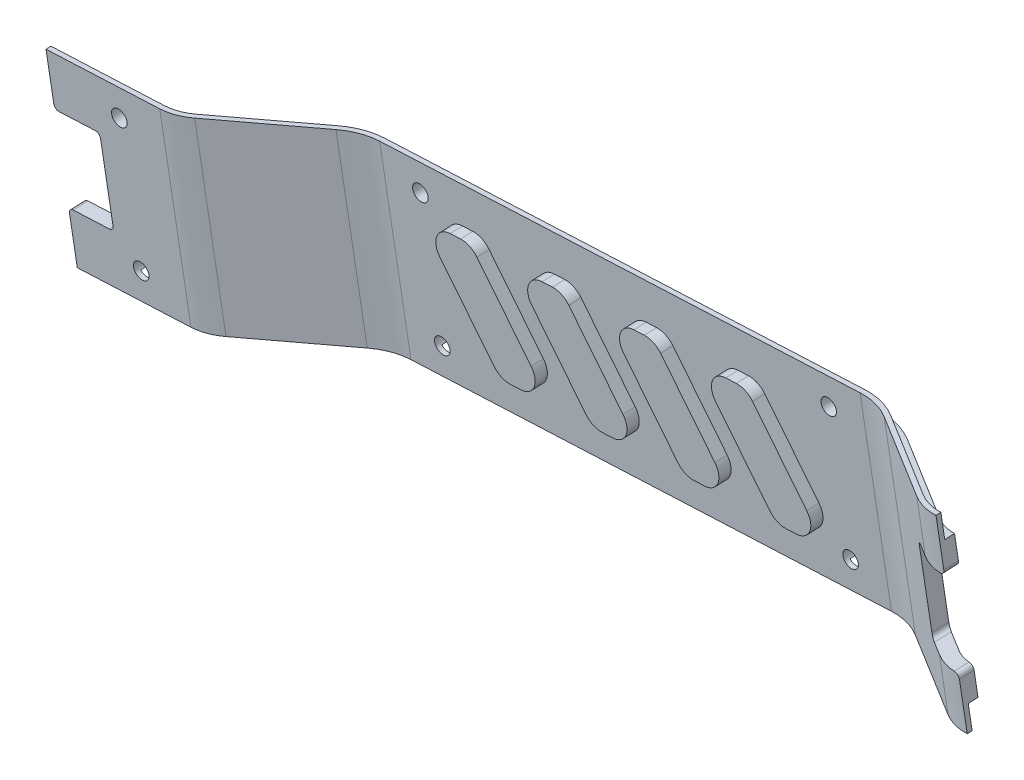
SolidWorks part; units mm, degrees
material "ABS"
ref_plane "前视基准面" through (0, 0, 0) normal (0, 0, 1) x (1, 0, 0)
ref_plane "上视基准面" through (0, 0, 0) normal (0, 1, 0) x (1, 0, 0)
ref_plane "右视基准面" through (0, 0, 0) normal (1, 0, 0) x (0, 0, -1)
other "Configuration Table"
sketch "草图2" plane through (-35.9528, 399.7424, 30.5662) normal (-0.0893, 0.9931, 0.0759) x (0.996, 0.0891, 0.0068)
  line L0 (491.2635, -1135.8026) -> (472.3863, -1123.9958) construction
  line L1 (464.962, -1121.7226) -> (358.5246, -1117.9612) construction
  line L2 (350.9583, -1119.7047) -> (331.2948, -1130.1494) construction
  line L3 (325.2417, -1131.5442) -> (302.5393, -1130.7419) construction
  line L4 (491.2635, -1135.8026) -> (472.3863, -1123.9958)
  line L5 (464.962, -1121.7226) -> (358.5246, -1117.9612)
  line L6 (350.9583, -1119.7047) -> (331.2948, -1130.1494)
  line L7 (325.2417, -1131.5442) -> (302.5393, -1130.7419)
  line L8 (492.8543, -1133.2591) -> (473.9771, -1121.4523)
  line L9 (465.0679, -1118.7245) -> (358.6305, -1114.9631)
  line L10 (349.551, -1117.0552) -> (329.8875, -1127.5)
  line L11 (325.3477, -1128.5461) -> (302.6452, -1127.7438)
  line L12 (302.6452, -1127.7438) -> (302.5393, -1130.7419)
  line L13 (497.3089, -1134.623) -> (497.203, -1137.6212)
  arc A0 (491.2635, -1135.8026) -> (497.203, -1137.6212) centre (497.6268, -1125.6286) ccw construction
  arc A1 (472.3863, -1123.9958) -> (464.962, -1121.7226) centre (464.4322, -1136.7132) ccw construction
  arc A2 (358.5246, -1117.9612) -> (350.9583, -1119.7047) centre (357.9948, -1132.9518) ccw construction
  arc A3 (325.2417, -1131.5442) -> (331.2948, -1130.1494) centre (325.6655, -1119.5517) ccw construction
  arc A4 (491.2635, -1135.8026) -> (497.203, -1137.6212) centre (497.6268, -1125.6286) ccw
  arc A5 (472.3863, -1123.9958) -> (464.962, -1121.7226) centre (464.4322, -1136.7132) ccw
  arc A6 (358.5246, -1117.9612) -> (350.9583, -1119.7047) centre (357.9948, -1132.9518) ccw
  arc A7 (325.2417, -1131.5442) -> (331.2948, -1130.1494) centre (325.6655, -1119.5517) ccw
  arc A8 (492.8543, -1133.2591) -> (497.3089, -1134.623) centre (497.6268, -1125.6286) ccw
  arc A9 (473.9771, -1121.4523) -> (465.0679, -1118.7245) centre (464.4322, -1136.7132) ccw
  arc A10 (358.6305, -1114.9631) -> (349.551, -1117.0552) centre (357.9948, -1132.9518) ccw
  arc A11 (325.3477, -1128.5461) -> (329.8875, -1127.5) centre (325.6655, -1119.5517) ccw
  dimension "D1" = 3
extrude "凸台-拉伸1" add sketch "草图2" against normal up to surface (40 mm away)
sketch "草图3" plane through (-35.9528, 399.7424, 30.5662) normal (-0.0893, 0.9931, 0.0759) x (0.996, 0.0891, 0.0068)
  line L4 (492.8543, -1133.2591) -> (473.9771, -1121.4523) construction
  line L5 (465.0679, -1118.7245) -> (358.6305, -1114.9631) construction
  line L6 (349.551, -1117.0552) -> (329.8875, -1127.5) construction
  line L7 (325.3477, -1128.5461) -> (302.6452, -1127.7438) construction
  line L8 (472.9166, -1123.148) -> (491.7938, -1134.9547)
  line L9 (358.5599, -1116.9618) -> (464.9973, -1120.7232)
  line L10 (330.8257, -1129.2663) -> (350.4892, -1118.8215)
  line L11 (302.5746, -1129.7426) -> (325.2771, -1130.5448)
  line L12 (472.9166, -1123.148) -> (491.7938, -1134.9547)
  line L13 (358.5599, -1116.9618) -> (464.9973, -1120.7232)
  line L14 (330.8257, -1129.2663) -> (350.4892, -1118.8215)
  line L15 (302.5746, -1129.7426) -> (325.2771, -1130.5448)
  line L16 (492.8543, -1133.2591) -> (473.9771, -1121.4523)
  line L17 (465.0679, -1118.7245) -> (358.6305, -1114.9631)
  line L18 (349.551, -1117.0552) -> (329.8875, -1127.5)
  line L19 (325.3477, -1128.5461) -> (302.6452, -1127.7438)
  line L20 (302.6452, -1127.7438) -> (302.5746, -1129.7426)
  line L21 (497.3089, -1134.623) -> (497.2383, -1136.6218)
  arc A4 (492.8543, -1133.2591) -> (497.3089, -1134.623) centre (497.6268, -1125.6286) ccw construction
  arc A5 (473.9771, -1121.4523) -> (465.0679, -1118.7245) centre (464.4322, -1136.7132) ccw construction
  arc A6 (358.6305, -1114.9631) -> (349.551, -1117.0552) centre (357.9948, -1132.9518) ccw construction
  arc A7 (325.3477, -1128.5461) -> (329.8875, -1127.5) centre (325.6655, -1119.5517) ccw construction
  arc A8 (491.7938, -1134.9547) -> (497.2383, -1136.6218) centre (497.6268, -1125.6286) ccw
  arc A9 (472.9166, -1123.148) -> (464.9973, -1120.7232) centre (464.4322, -1136.7132) ccw
  arc A10 (358.5599, -1116.9618) -> (350.4892, -1118.8215) centre (357.9948, -1132.9518) ccw
  arc A11 (325.2771, -1130.5448) -> (330.8257, -1129.2663) centre (325.6655, -1119.5517) ccw
  arc A12 (491.7938, -1134.9547) -> (497.2383, -1136.6218) centre (497.6268, -1125.6286) ccw
  arc A13 (472.9166, -1123.148) -> (464.9973, -1120.7232) centre (464.4322, -1136.7132) ccw
  arc A14 (358.5599, -1116.9618) -> (350.4892, -1118.8215) centre (357.9948, -1132.9518) ccw
  arc A15 (325.2771, -1130.5448) -> (330.8257, -1129.2663) centre (325.6655, -1119.5517) ccw
  arc A16 (492.8543, -1133.2591) -> (497.3089, -1134.623) centre (497.6268, -1125.6286) ccw
  arc A17 (473.9771, -1121.4523) -> (465.0679, -1118.7245) centre (464.4322, -1136.7132) ccw
  arc A18 (358.6305, -1114.9631) -> (349.551, -1117.0552) centre (357.9948, -1132.9518) ccw
  arc A19 (325.3477, -1128.5461) -> (329.8875, -1127.5) centre (325.6655, -1119.5517) ccw
  dimension "D1" = 1
extrude "切除-拉伸1" cut sketch "草图3" against normal blind 5
sketch "草图5" plane through (-38.7497, -87.401, 1097.4452) normal (0.0352, 0.0793, -0.9962) x (-0.9994, 0.0028, -0.0351)
  circle A0 centre (-458.8628, 439.2871) radius 1.6 construction
  circle A1 centre (-368.7211, 431.1983) radius 1.6 construction
  circle A2 centre (-458.8628, 439.2871) radius 1.6 construction
  circle A3 centre (-368.7211, 431.1983) radius 1.6 construction
  circle A4 centre (-458.8628, 439.2871) radius 1.7
  circle A5 centre (-368.7211, 431.1983) radius 1.7
  dimension "D1" = 3.4
  dimension "D2" = 3.4
extrude "切除-拉伸2" cut sketch "草图5" against normal blind 10
sketch "草图6" plane through (-39.3741, -88.8093, 1115.1282) normal (-0.0352, -0.0793, 0.9962) x (0.9994, -0.0028, 0.0351)
  circle A0 centre (318.142, 426.6596) radius 1.6 construction
  circle A1 centre (318.142, 426.6596) radius 1.6 construction
  circle A2 centre (318.142, 426.6596) radius 1.7
  dimension "D1" = 3.4
extrude "切除-拉伸3" cut sketch "草图6" against normal blind 55
sketch "草图7" plane through (-39.2686, -88.5713, 1112.1395) normal (0.0352, 0.0793, -0.9962) x (-0.9994, 0.0028, -0.0351)
  line L0 (-323.1718, 427.111) -> (-323.0824, 428.107)
  line L1 (-319.4219, 427.7785) -> (-328.0126, 428.5494) construction
  line L2 (-323.0824, 428.107) -> (-313.0228, 427.2043)
  line L3 (-305.3869, 426.5191) -> (-316.6833, 427.5328) construction
  line L4 (-313.0228, 427.2043) -> (-313.1122, 426.2083)
  arc A0 (-323.1718, 427.111) -> (-313.1122, 426.2083) centre (-318.142, 426.6596) ccw
  dimension "D1" = 10.1
  dimension "D2" = 90
extrude "切除-拉伸4" cut sketch "草图7" against normal blind 0.8
ref_plane "基准面2" through (-34.1664, 379.8803, 29.0475) normal (-0.0893, 0.9931, 0.0759) x (0.996, 0.0891, 0.0068)
mirror "镜向2" about plane through (-34.1664, 379.8803, 29.0475) normal (-0.0893, 0.9931, 0.0759) of "切除-拉伸4", "切除-拉伸3", "切除-拉伸2", "切除-拉伸1"
sketch "草图8" plane through (340.7041, 29.5431, 14.3828) normal (-0.9954, -0.0863, -0.042) x (-0.0419, -0.0036, 0.9991)
  line L0 (1143.6671, 276.3937) -> (1146.7072, 316.278) construction
  line L1 (1145.7101, 316.354) -> (1146.7072, 316.278) construction
  line L2 (1145.3301, 311.3685) -> (1145.7101, 316.354) construction
  line L3 (1143.3359, 311.5205) -> (1145.3301, 311.3685) construction
  line L4 (1141.0558, 281.6073) -> (1143.3359, 311.5205) construction
  line L5 (1143.05, 281.4553) -> (1142.6699, 276.4697) construction
  line L6 (1142.6699, 276.4697) -> (1143.6671, 276.3937) construction
  line L7 (1141.0558, 281.6073) -> (1143.05, 281.4553) construction
  line L16 (1141.0558, 281.6073) -> (1143.05, 281.4553)
  line L17 (1143.05, 281.4553) -> (1142.6699, 276.4697)
  line L18 (1142.6699, 276.4697) -> (1143.6671, 276.3937)
  line L19 (1143.6671, 276.3937) -> (1146.7072, 316.278)
  line L20 (1146.7072, 316.278) -> (1145.7101, 316.354)
  line L21 (1145.7101, 316.354) -> (1145.3301, 311.3685)
  line L22 (1145.3301, 311.3685) -> (1143.3359, 311.5205)
  line L23 (1143.3359, 311.5205) -> (1141.0558, 281.6073)
extrude "凸台-拉伸2" add sketch "草图8" along normal blind 2.5
sketch "草图9" plane through (-38.8552, -87.6391, 1100.4339) normal (-0.0352, -0.0793, 0.9962) x (0.9994, -0.0028, 0.0351)
  line L3 (435.8978, 429.2946) -> (446.5285, 414.1843)
  line L4 (449.976, 412.586) -> (452.2762, 412.7924)
  line L5 (455.0445, 418.7637) -> (444.4138, 433.8741)
  line L6 (440.9663, 435.4723) -> (438.6661, 435.2659)
  line L7 (435.7343, 429.1795) -> (446.3649, 414.0692)
  line L8 (440.9484, 435.6715) -> (438.6483, 435.4651)
  line L9 (455.208, 418.8788) -> (444.5774, 433.9891)
  line L10 (449.9939, 412.3868) -> (452.294, 412.5932)
  line L11 (435.7343, 429.1795) -> (446.3649, 414.0692) construction
  line L12 (440.9484, 435.6715) -> (438.6483, 435.4651) construction
  line L13 (455.208, 418.8788) -> (444.5774, 433.9891) construction
  line L14 (449.9939, 412.3868) -> (452.294, 412.5932) construction
  line L15 (415.449, 427.3593) -> (426.0796, 412.2489)
  line L16 (420.6631, 433.8513) -> (418.363, 433.6449)
  line L17 (434.9227, 417.0585) -> (424.2921, 432.1689)
  line L18 (429.7086, 410.5665) -> (432.0088, 410.7729)
  line L19 (415.449, 427.3593) -> (426.0796, 412.2489) construction
  line L20 (420.6631, 433.8513) -> (418.363, 433.6449) construction
  line L21 (434.9227, 417.0585) -> (424.2921, 432.1689) construction
  line L22 (429.7086, 410.5665) -> (432.0088, 410.7729) construction
  line L23 (395.1637, 425.539) -> (405.7943, 410.4286)
  line L24 (400.3778, 432.031) -> (398.0777, 431.8246)
  line L25 (414.6374, 415.2382) -> (404.0068, 430.3486)
  line L26 (409.4233, 408.7462) -> (411.7235, 408.9526)
  line L27 (395.1637, 425.539) -> (405.7943, 410.4286) construction
  line L28 (400.3778, 432.031) -> (398.0777, 431.8246) construction
  line L29 (414.6374, 415.2382) -> (404.0068, 430.3486) construction
  line L30 (409.4233, 408.7462) -> (411.7235, 408.9526) construction
  line L31 (374.8784, 423.7187) -> (385.509, 408.6083)
  line L32 (380.0925, 430.2107) -> (377.7924, 430.0043)
  line L33 (394.3521, 413.4179) -> (383.7215, 428.5283)
  line L34 (389.138, 406.9259) -> (391.4382, 407.1323)
  line L35 (374.8784, 423.7187) -> (385.509, 408.6083) construction
  line L36 (380.0925, 430.2107) -> (377.7924, 430.0043) construction
  line L37 (394.3521, 413.4179) -> (383.7215, 428.5283) construction
  line L38 (389.138, 406.9259) -> (391.4382, 407.1323) construction
  line L39 (415.6125, 427.4743) -> (426.2432, 412.364)
  line L40 (429.6907, 410.7657) -> (431.9909, 410.9721)
  line L41 (434.7592, 416.9434) -> (424.1285, 432.0538)
  line L42 (420.681, 433.6521) -> (418.3808, 433.4457)
  line L43 (395.3272, 425.6541) -> (405.9579, 410.5437)
  line L44 (409.4054, 408.9454) -> (411.7056, 409.1518)
  line L45 (414.4739, 415.1231) -> (403.8432, 430.2335)
  line L46 (400.3957, 431.8318) -> (398.0955, 431.6254)
  line L47 (375.0419, 423.8338) -> (385.6726, 408.7234)
  line L48 (389.1201, 407.1251) -> (391.4203, 407.3315)
  line L49 (394.1886, 413.3029) -> (383.5579, 428.4132)
  line L50 (380.1104, 430.0115) -> (377.8102, 429.8051)
  arc A4 (446.5285, 414.1843) -> (449.976, 412.586) centre (449.6364, 416.3708) ccw
  arc A5 (452.2762, 412.7924) -> (455.0445, 418.7637) centre (451.9365, 416.5772) ccw
  arc A6 (444.4138, 433.8741) -> (440.9663, 435.4723) centre (441.3059, 431.6875) ccw
  arc A7 (438.6661, 435.2659) -> (435.8978, 429.2946) centre (439.0058, 431.4811) ccw
  arc A8 (438.6483, 435.4651) -> (435.7343, 429.1795) centre (439.0058, 431.4811) ccw
  arc A9 (444.5774, 433.9891) -> (440.9484, 435.6715) centre (441.3059, 431.6875) ccw
  arc A10 (452.294, 412.5932) -> (455.208, 418.8788) centre (451.9365, 416.5772) ccw
  arc A11 (446.3649, 414.0692) -> (449.9939, 412.3868) centre (449.6364, 416.3708) ccw
  arc A12 (438.6483, 435.4651) -> (435.7343, 429.1795) centre (439.0058, 431.4811) ccw construction
  arc A13 (444.5774, 433.9891) -> (440.9484, 435.6715) centre (441.3059, 431.6875) ccw construction
  arc A14 (452.294, 412.5932) -> (455.208, 418.8788) centre (451.9365, 416.5772) ccw construction
  arc A15 (446.3649, 414.0692) -> (449.9939, 412.3868) centre (449.6364, 416.3708) ccw construction
  arc A16 (418.363, 433.6449) -> (415.449, 427.3593) centre (418.7205, 429.6609) ccw
  arc A17 (424.2921, 432.1689) -> (420.6631, 433.8513) centre (421.0206, 429.8673) ccw
  arc A18 (432.0088, 410.7729) -> (434.9227, 417.0585) centre (431.6513, 414.7569) ccw
  arc A19 (426.0796, 412.2489) -> (429.7086, 410.5665) centre (429.3511, 414.5505) ccw
  arc A20 (418.363, 433.6449) -> (415.449, 427.3593) centre (418.7205, 429.6609) ccw construction
  arc A21 (424.2921, 432.1689) -> (420.6631, 433.8513) centre (421.0206, 429.8673) ccw construction
  arc A22 (432.0088, 410.7729) -> (434.9227, 417.0585) centre (431.6513, 414.7569) ccw construction
  arc A23 (426.0796, 412.2489) -> (429.7086, 410.5665) centre (429.3511, 414.5505) ccw construction
  arc A24 (398.0777, 431.8246) -> (395.1637, 425.539) centre (398.4352, 427.8406) ccw
  arc A25 (404.0068, 430.3486) -> (400.3778, 432.031) centre (400.7353, 428.047) ccw
  arc A26 (411.7235, 408.9526) -> (414.6374, 415.2382) centre (411.366, 412.9366) ccw
  arc A27 (405.7943, 410.4286) -> (409.4233, 408.7462) centre (409.0658, 412.7302) ccw
  arc A28 (398.0777, 431.8246) -> (395.1637, 425.539) centre (398.4352, 427.8406) ccw construction
  arc A29 (404.0068, 430.3486) -> (400.3778, 432.031) centre (400.7353, 428.047) ccw construction
  arc A30 (411.7235, 408.9526) -> (414.6374, 415.2382) centre (411.366, 412.9366) ccw construction
  arc A31 (405.7943, 410.4286) -> (409.4233, 408.7462) centre (409.0658, 412.7302) ccw construction
  arc A32 (377.7924, 430.0043) -> (374.8784, 423.7187) centre (378.1499, 426.0203) ccw
  arc A33 (383.7215, 428.5283) -> (380.0925, 430.2107) centre (380.45, 426.2267) ccw
  arc A34 (391.4382, 407.1323) -> (394.3521, 413.4179) centre (391.0807, 411.1163) ccw
  arc A35 (385.509, 408.6083) -> (389.138, 406.9259) centre (388.7805, 410.9099) ccw
  arc A36 (377.7924, 430.0043) -> (374.8784, 423.7187) centre (378.1499, 426.0203) ccw construction
  arc A37 (383.7215, 428.5283) -> (380.0925, 430.2107) centre (380.45, 426.2267) ccw construction
  arc A38 (391.4382, 407.1323) -> (394.3521, 413.4179) centre (391.0807, 411.1163) ccw construction
  arc A39 (385.509, 408.6083) -> (389.138, 406.9259) centre (388.7805, 410.9099) ccw construction
  arc A40 (426.2432, 412.364) -> (429.6907, 410.7657) centre (429.3511, 414.5505) ccw
  arc A41 (431.9909, 410.9721) -> (434.7592, 416.9434) centre (431.6513, 414.7569) ccw
  arc A42 (424.1285, 432.0538) -> (420.681, 433.6521) centre (421.0206, 429.8673) ccw
  arc A43 (418.3808, 433.4457) -> (415.6125, 427.4743) centre (418.7205, 429.6609) ccw
  arc A44 (405.9579, 410.5437) -> (409.4054, 408.9454) centre (409.0658, 412.7302) ccw
  arc A45 (411.7056, 409.1518) -> (414.4739, 415.1231) centre (411.366, 412.9366) ccw
  arc A46 (403.8432, 430.2335) -> (400.3957, 431.8318) centre (400.7353, 428.047) ccw
  arc A47 (398.0955, 431.6254) -> (395.3272, 425.6541) centre (398.4352, 427.8406) ccw
  arc A48 (385.6726, 408.7234) -> (389.1201, 407.1251) centre (388.7805, 410.9099) ccw
  arc A49 (391.4203, 407.3315) -> (394.1886, 413.3029) centre (391.0807, 411.1163) ccw
  arc A50 (383.5579, 428.4132) -> (380.1104, 430.0115) centre (380.45, 426.2267) ccw
  arc A51 (377.8102, 429.8051) -> (375.0419, 423.8338) centre (378.1499, 426.0203) ccw
  dimension "D1" = 0
  dimension "D2" = 0
  dimension "D3" = 0
  dimension "D4" = 0
  dimension "D5" = 0.2
extrude "凸台-拉伸3" add sketch "草图9" along normal blind 2.5
fillet "圆角1" radius 2.2 4 edges at (276.2261, 306.5856, 1155.1513) (286.2794, 307.4574, 1155.5757) (283.5998, 337.2505, 1157.8539) (273.5465, 336.3787, 1157.4295)
sketch "草图10" plane through (-39.3741, -88.8093, 1115.1282) normal (-0.0352, -0.0793, 0.9962) x (0.9994, -0.0028, 0.0351)
  line L0 (304.2375, 411.3557) -> (329.3532, 413.6094) construction
  line L1 (306.025, 391.4357) -> (302.45, 431.2756) construction
  line L2 (331.1407, 393.6895) -> (327.5657, 433.5294) construction
  line L3 (303.4331, 420.3197) -> (305.0419, 402.3917)
  line L4 (305.0419, 402.3917) -> (315.0019, 403.2854)
  line L5 (315.0019, 403.2854) -> (313.3931, 421.2134)
  line L6 (313.3931, 421.2134) -> (303.4331, 420.3197)
  point P8 (314.1975, 412.2494)
  dimension "D1" = 10
  dimension "D2" = 18
extrude "切除-拉伸5" cut sketch "草图10" against normal blind 10
fillet "圆角2" radius 1 4 edges at (275.4856, 312.4426, 1156.6958) (265.5318, 311.5795, 1156.2756) (273.8778, 330.3185, 1158.0627) (263.924, 329.4553, 1157.6425)
sketch "草图11" plane through (-39.3741, -88.8093, 1115.1282) normal (-0.0352, -0.0793, 0.9962) x (0.9994, -0.0028, 0.0351)
  line L0 (475.552, 426.7284) -> (500.7332, 428.9881) construction
  line L1 (477.3395, 406.8085) -> (473.7645, 446.6484) construction
  line L2 (502.5207, 409.0681) -> (498.9457, 448.908) construction
  line L3 (489.9688, 437.0583) -> (491.5776, 419.1303)
  line L5 (491.5776, 419.1303) -> (501.5376, 420.0241)
  line L6 (501.5376, 420.0241) -> (499.9288, 437.952)
  line L7 (499.9288, 437.952) -> (489.9688, 437.0583)
  point P10 (490.7732, 428.0943)
  dimension "D1" = 18
  dimension "D2" = 10
extrude "切除-拉伸6" cut sketch "草图11" against normal blind 10
fillet "圆角3" radius 1 4 edges at (461.9059, 328.6075, 1164.5655) (460.2981, 346.4833, 1165.9324) (450.4902, 345.9494, 1161.3787) (452.098, 328.0735, 1160.0118)
